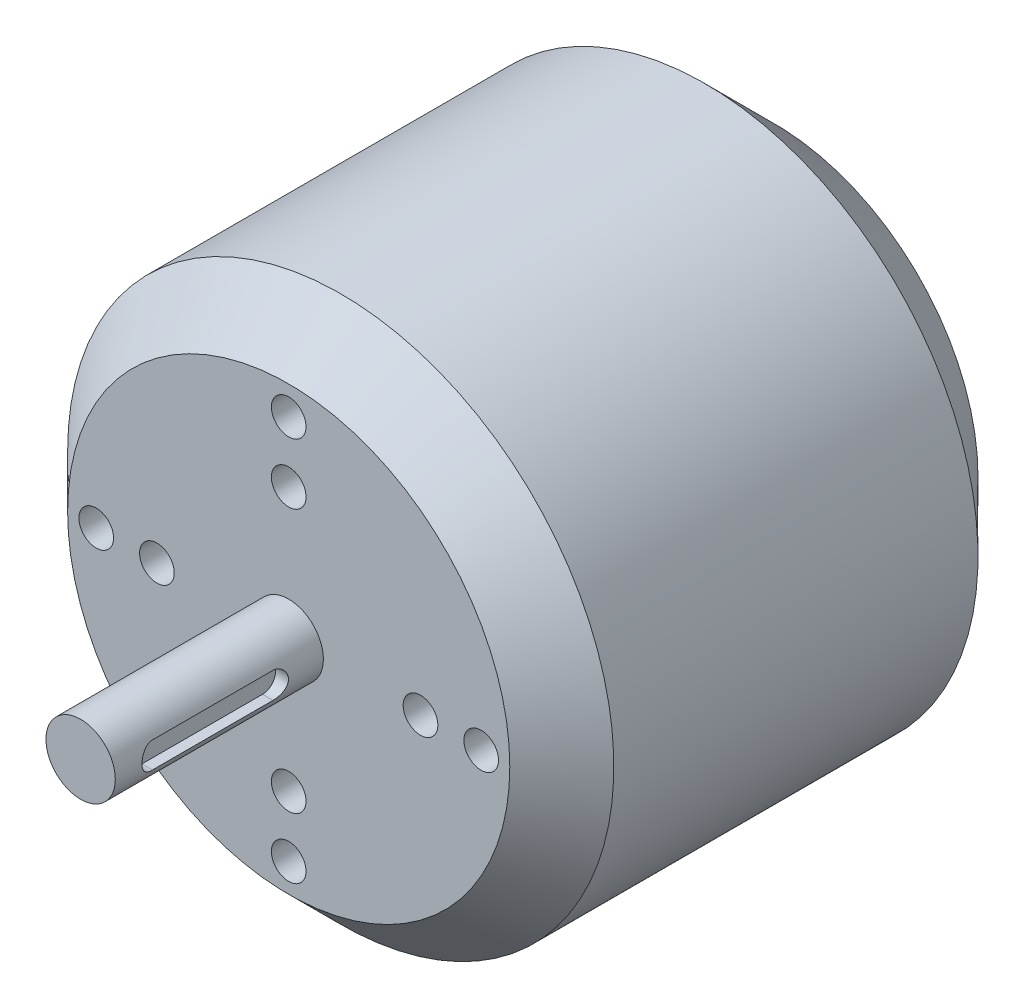
SolidWorks part; units mm, degrees
material "6061-T6 (SS)"
ref_plane "Front Plane" through (0, 0, 0) normal (0, 0, 1) x (1, 0, 0)
ref_plane "Top Plane" through (0, 0, 0) normal (0, 1, 0) x (1, 0, 0)
ref_plane "Right Plane" through (0, 0, 0) normal (1, 0, 0) x (0, 0, -1)
sketch "Sketch1" plane through (0, 0, 0) normal (0, 0, 1) x (1, 0, 0)
  circle A0 centre (0, 0) radius 31.5
  dimension "D1" = 63
extrude "Boss-Extrude1" add sketch "Sketch1" along normal blind 42
sketch "Sketch2" plane through (0, 0, 42) normal (0, 0, 1) x (1, 0, 0)
  circle A0 centre (0, 0) radius 31.5
extrude "Boss-Extrude2" add sketch "Sketch2" along normal blind 6
chamfer "Chamfer1" distance 6 distance2 6 1 edges at (31.5, 0, 48)
ref_plane "Plane1" through (0, 0, 33) normal (0, 0, 1) x (1, 0, 0)
sketch "Sketch4" plane through (0, 0, 0) normal (0, 0, -1) x (-1, 0, 0)
  circle A0 centre (0, 0) radius 31.5
extrude "Boss-Extrude3" add sketch "Sketch4" along normal blind 8
ref_plane "Plane2" through (0, 0, 2) normal (0, 0, -1) x (-1, 0, 0)
chamfer "Chamfer2" distance 8 distance2 8 1 edges at (-31.5, 0, -8)
sketch "Sketch6" plane through (0, 0, -8) normal (0, 0, -1) x (-1, 0, 0)
  circle A0 centre (0, 0) radius 7.5
  dimension "D1" = 15
extrude "Boss-Extrude4" add sketch "Sketch6" along normal blind 1
sketch "Sketch7" plane through (0, 0, 48) normal (0, 0, 1) x (1, 0, 0)
  circle A0 centre (0, 0) radius 4
  dimension "D1" = 8
extrude "Boss-Extrude5" add sketch "Sketch7" along normal blind 24
sketch "Sketch10" plane through (0, 0, 48) normal (0, 0, 1) x (1, 0, 0)
  circle A0 centre (0, 15.2) radius 2
  circle A1 centre (0, 22.2) radius 2
  circle A2 centre (22.2, 0) radius 2
  circle A3 centre (15.2, 0) radius 2
  circle A4 centre (0, -22.2) radius 2
  circle A5 centre (0, -15.2) radius 2
  circle A6 centre (-22.2, 0) radius 2
  circle A7 centre (-15.2, 0) radius 2
  point P20 (0, 0)
  dimension "D1" = 4
  dimension "D2" = 4
  dimension "D4" = 22.2
  dimension "D3" = 15.2
  dimension "D5" = 4
extrude "Cut-Extrude4" cut sketch "Sketch10" against normal blind 8
ref_axis "Hip_Axis_b" through (0, 0, 42) along (0, 0, -1)
ref_plane "Plane3" through (2.5, 0, 0) normal (1, 0, 0) x (0, 0, -1)
sketch "Sketch11" plane through (2.5, 0, 0) normal (1, 0, 0) x (0, 0, -1)
  line L0 (-67.4185, 0) -> (-53.5271, 0) construction
  line L1 (-67.4185, 1.5) -> (-53.5271, 1.5)
  line L2 (-67.4185, -1.5) -> (-53.5271, -1.5)
  arc A0 (-67.4185, 1.5) -> (-67.4185, -1.5) centre (-67.4185, 0) ccw
  arc A1 (-53.5271, -1.5) -> (-53.5271, 1.5) centre (-53.5271, 0) ccw
  point P3 (-60.4728, 0)
  dimension "D1" = 3
extrude "Cut-Extrude5" cut sketch "Sketch11" along normal blind 10
